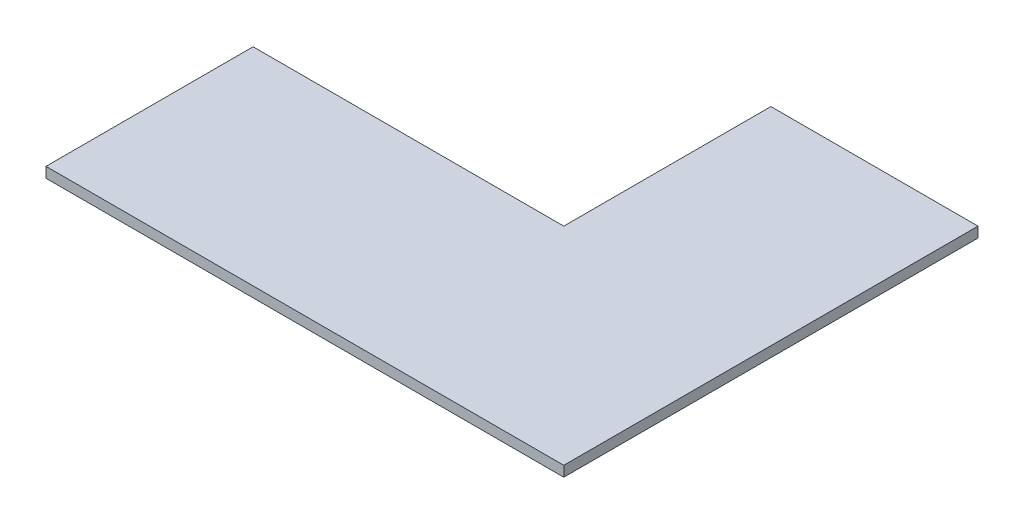
SolidWorks part; units mm, degrees
material "AISI 304"
ref_plane "前视基准面" through (0, 0, 0) normal (0, 0, 1) x (1, 0, 0)
ref_plane "上视基准面" through (0, 0, 0) normal (0, 1, 0) x (1, 0, 0)
ref_plane "右视基准面" through (0, 0, 0) normal (1, 0, 0) x (0, 0, -1)
sketch "草图1" plane through (0, 0, 0) normal (0, 1, 0) x (1, 0, 0)
  line L0 (0, 0) -> (0, 40)
  line L1 (0, 40) -> (40, 40)
  line L2 (40, 40) -> (40, -40)
  line L3 (40, -40) -> (-60, -40)
  line L4 (-60, -40) -> (-60, 0)
  line L5 (-60, 0) -> (0, 0)
  dimension "D1" = 40
  dimension "D2" = 100
  dimension "D3" = 80
  dimension "D4" = 40
base flange "基体-法兰1" sketch "草图1" thickness 2 reverse thickness direction no parameters "D1"=0.7366
sketch "折弯-线1" [suppressed] plane through (0, 0, 0) normal (0, 1, 0) x (1, 0, 0)
sketch "边界框1" [suppressed] plane through (0, 0, 0) normal (0, 1, 0) x (1, 0, 0)
sheet metal parameters "钣金6" thickness 2 parameters "D1"=0.7366
flat pattern "平板型式6" [suppressed]
sketch "折弯-线2" plane through (0, 0, 0) normal (0, 1, 0) x (1, 0, 0)
sketch3d "边界框2" [suppressed]
  line L0 (40, -40, 0) -> (-60, -40, 0) construction
  line L1 (40, 40, 0) -> (-60, 40, 0) construction
  line L2 (40, -40, 0) -> (40, 40, 0) construction
  line L3 (-60, -40, 0) -> (-60, 40, 0) construction
